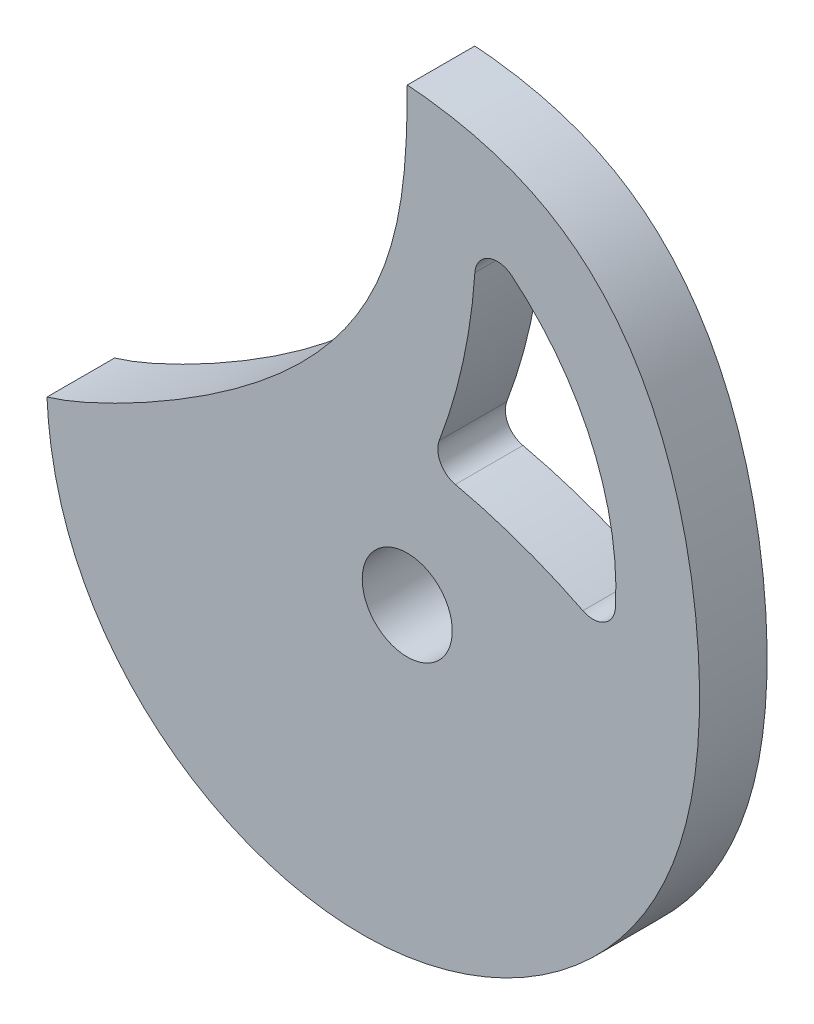
SolidWorks part; units mm, degrees
ref_plane "Front Plane" through (0, 0, 0) normal (0, 0, 1) x (1, 0, 0)
ref_plane "Top Plane" through (0, 0, 0) normal (0, 1, 0) x (1, 0, 0)
ref_plane "Right Plane" through (0, 0, 0) normal (1, 0, 0) x (0, 0, -1)
ref_plane "Plane1" through (0, 0, 0) normal (0, 0, -1) x (-1, 0, 0)
sketch "Sketch1" plane through (0, 0, 0) normal (0, 0, -1) x (-1, 0, 0)
  circle A0 centre (0, 0) radius 12.7
  arc A1 (-58.7073, 28.7043) -> (-29.4195, 95.1955) centre (21.1653, 33.2182) cw
  arc A2 (-29.4195, 95.1955) -> (-19.0686, 90.7021) centre (-25.4043, 90.2761) cw
  arc A3 (-19.0686, 90.7021) -> (-9.0222, 44.6754) centre (140.5708, 101.4375) ccw
  arc A4 (-9.0222, 44.6754) -> (-13.5611, 36.2285) centre (-14.9592, 42.4227) cw
  arc A5 (-13.5611, 36.2285) -> (-49.5252, 23.3842) centre (21.2545, -118.0273) ccw
  arc A6 (-49.5252, 23.3842) -> (-58.7073, 28.7043) centre (-52.3674, 29.0626) cw
  spline S0 degree 5 poles (101.6, 0) (101.3221, -6.1365) (99.9658, -17.9529) (95.5299, -34.3083) (85.0746, -53.2436) (65.9914, -71.4303) (42.9865, -83.3334) (18.2709, -88.3871) (-6.0804, -86.434) (-28.7704, -78.33) (-48.6255, -65.1605) (-64.5061, -47.9243) (-75.6549, -27.5607) (-81.729, -4.9389) (-83.305, 19.3723) (-81.4017, 44.6566) (-75.8896, 69.1059) (-66.5714, 90.7405) (-53.3534, 107.7515) (-36.9466, 119.0461) (-18.9813, 124.8162) (-7.108, 126.4503) (-1.8405, 126.9) (-0.2871, 127) (0, 127) knots -1 -1 -1 -1 -1 -1 -0.95 -0.9 -0.85 -0.8 -0.75 -0.7 -0.65 -0.6 -0.55 -0.5 -0.45 -0.4 -0.35 -0.3 -0.25 -0.2 -0.15 -0.1 -0.05 0 0 0 0 0 0
  spline S1 degree 5 poles (0, 127) (0, 125.4788) (0.0177, 122.257) (0.0972, 116.8859) (0.3989, 108.7197) (1.5971, 97.2581) (4.2051, 85.0941) (8.738, 72.808) (15.4433, 60.9012) (24.1564, 49.7136) (34.4456, 39.4692) (45.7073, 30.3015) (57.2694, 22.2807) (68.4816, 15.4341) (78.8164, 9.7638) (87.9482, 5.261) (94.1442, 2.5834) (98.1309, 1.0913) (100.4929, 0.3256) (101.6, 0) knots 0 0 0 0 0 0 0.066667 0.133333 0.2 0.266667 0.333333 0.4 0.466667 0.533333 0.6 0.666667 0.733333 0.8 0.866667 0.933333 1 1 1 1 1 1
extrude "Boss-Extrude1" add sketch "Sketch1" against normal blind 19.05
